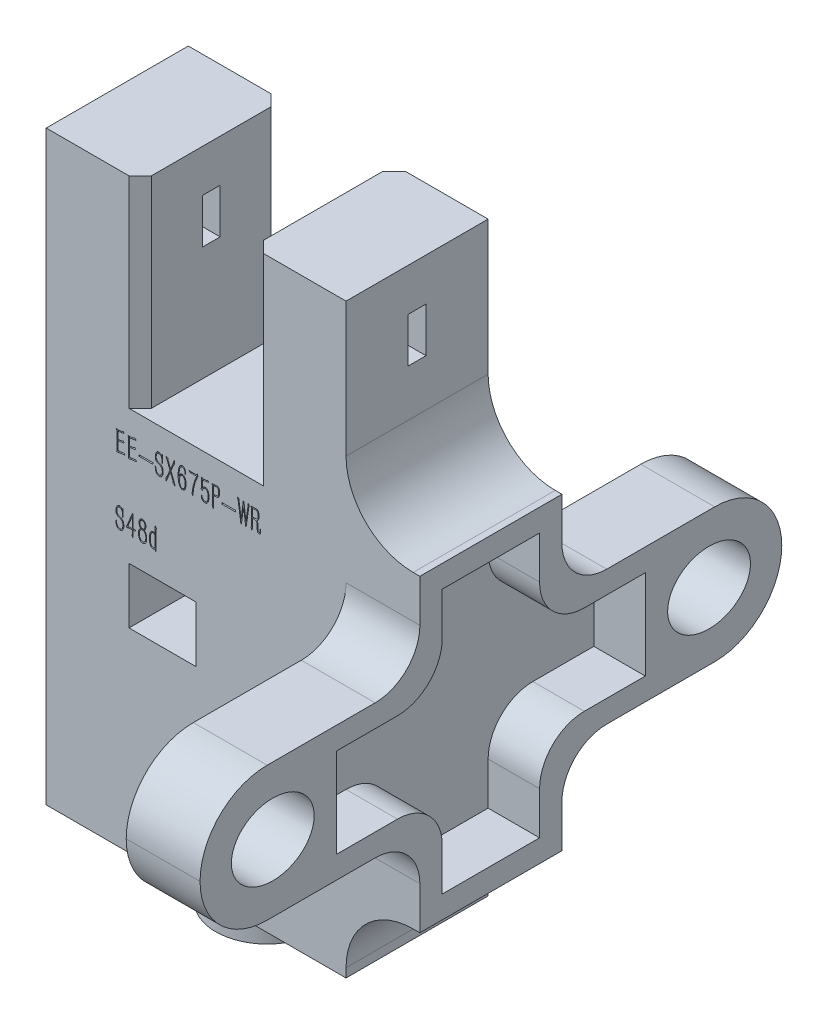
SolidWorks part; units mm, degrees
ref_plane "前视基准面" through (0, 0, 0) normal (0, 0, 1) x (1, 0, 0)
ref_plane "上视基准面" through (0, 0, 0) normal (0, 1, 0) x (1, 0, 0)
ref_plane "右视基准面" through (0, 0, 0) normal (1, 0, 0) x (0, 0, -1)
sketch "草图1" plane through (0, 0, 0) normal (0, 0, 1) x (1, 0, 0)
  line L12 (-6.7, 9) -> (-2.5, 9)
  line L13 (-2.5, 9) -> (-2.5, 0)
  line L14 (-2.5, 0) -> (2.5, 0)
  line L15 (2.5, 0) -> (2.5, 9)
  line L16 (2.5, 9) -> (6.7, 9)
  line L17 (6.7, 9) -> (6.7, 0)
  line L21 (6.7, -12.4475) -> (6.7, -17.2)
  line L22 (6.7, -17.2) -> (-6.7, -17.2)
  line L23 (-6.7, -17.2) -> (-6.7, 9)
  line L24 (0, 0) -> (0, 14.9355) construction
  line L25 (6.7, 0) -> (6.7, -12.4475)
  line L26 (-3, -8.5) -> (0, -8.5)
  line L27 (-3, -8.5) -> (-3, -6)
  line L28 (-3, -6) -> (0, -6)
  line L29 (0, -8.5) -> (0, -6)
  point P10 (0, 0)
  dimension "D1" = 13.4
  dimension "D2" = 5
  dimension "D3" = 9
  dimension "D4" = 8.5
  dimension "D5" = 2.5
  dimension "D6" = 3
  dimension "D7" = 6.7
  dimension "D8" = 13.4
  dimension "D10" = 26.2
extrude "凸台-拉伸1" add sketch "草图1" along normal blind 6.35
sketch "草图2" plane through (6.7, 0, 0) normal (1, 0, 0) x (0, 0, -1)
  line L0 (-16.175, -6.9) -> (11.6328, -6.9) construction
  line L1 (-6.35, -17.2) -> (0, -17.2) construction
  line L2 (-6.35, -3.9) -> (-16.175, -3.9)
  line L3 (-6.35, -17.2) -> (-6.35, 9) construction
  line L4 (-16.175, -3.9) -> (-16.175, -9.9)
  line L5 (-3.175, 9) -> (-3.175, 2.4392) construction
  line L6 (-6.35, 9) -> (0, 9) construction
  line L7 (0, -3.9) -> (9.825, -3.9)
  line L8 (9.825, -3.9) -> (9.825, -9.9)
  line L9 (-6.35, -9.9) -> (-16.175, -9.9)
  line L10 (0, -9.9) -> (9.825, -9.9)
  line L11 (-9.0117, 6.1) -> (2.8445, 6.1) construction
  line L12 (-3.575, 5.1) -> (-3.575, 7.1)
  line L13 (-3.575, 7.1) -> (-2.775, 7.1)
  line L14 (-2.775, 5.1) -> (-2.775, 7.1)
  line L15 (-3.575, 5.1) -> (-2.775, 5.1)
  line L16 (-6.35, -3.9) -> (0, -3.9)
  line L17 (-6.35, -9.9) -> (0, -9.9)
  line L18 (-6.35, -3.9) -> (-6.35, 0)
  line L19 (-6.35, 0) -> (0, 0)
  line L20 (0, 0) -> (0, -3.9)
  line L21 (-6.35, -9.9) -> (-6.35, -13.8)
  line L22 (-6.35, -13.8) -> (0, -13.8)
  line L23 (0, -17.2) -> (0, 9) construction
  line L24 (0, -13.8) -> (0, -9.9)
  line L25 (-5.35, -1) -> (-1, -1)
  line L26 (-1, -1) -> (-1, -4.9)
  line L27 (-1, -4.9) -> (3.725, -4.9)
  line L28 (3.725, -4.9) -> (3.725, -8.9)
  line L29 (3.725, -8.9) -> (-1, -8.9)
  line L30 (-1, -8.9) -> (-1, -12.8)
  line L31 (-1, -12.8) -> (-5.35, -12.8)
  line L32 (-5.35, -12.8) -> (-5.35, -8.9)
  line L33 (-5.35, -8.9) -> (-10.075, -8.9)
  line L34 (-10.075, -8.9) -> (-10.075, -4.9)
  line L35 (-10.075, -4.9) -> (-5.35, -4.9)
  line L36 (-5.35, -4.9) -> (-5.35, -1)
  ellipse E0 centre (-12.925, -6.9) end of major axis (-11.075, -6.9) minor radius 1.6
  ellipse E1 centre (6.575, -6.9) end of major axis (8.425, -6.9) minor radius 1.6
  point P30 (9.825, -6.9)
  point P37 (-3.175, 7.1)
  point P39 (-2.775, 6.1)
  point P40 (-3.575, 6.1)
  point P59 (-6.35, -11.85)
  line M11 (0, -17.2) -> (0, 9)
  line M13 (-6.35, 9) -> (-6.35, -17.2)
  dimension "D4" = 3.7
  dimension "D5" = 3
  dimension "D1" = 10.3
  dimension "D2" = 3.2
  dimension "D3" = 26
  dimension "D6" = 19.5
  dimension "D7" = 13
  dimension "D8" = 0.4
  dimension "D9" = 1
  dimension "D10" = 3.9
  dimension "D11" = 1
  dimension "D12" = 1
  dimension "D13" = 1
  dimension "D14" = 1
  dimension "D15" = 1
  dimension "D16" = 1
  dimension "D17" = 1
  dimension "D18" = 1
  dimension "D19" = 1
  dimension "D20" = 1
  dimension "D21" = 1
  dimension "D22" = 1
extrude "切除-拉伸1" cut sketch "草图2" against normal blind 16.35 contours L12 L15 L14 L13 region at (6.7, 6.1, 3.175)
extrude "凸台-拉伸2" add sketch "草图2<4>" along normal blind 1 contours L9 L2 L4 E0 M13 | L19 L16 M13 M11 | L22 L17 M13 M11 | L10 L8 L7 E1 M11 | L35 L36 L16 M13 | L26 L27 L16 M11 | L29 L30 L17 M11 | L32 L33 L17 M13 | L35 L34 L33 M13 | L36 L35 L33 L32 L17 L30 L29 L27 L26 L16 M13 M11 | L36 L16 L26 L25 | L32 L31 L30 L17 | L29 L28 L27 M11 region at (6.7, -4.4, 6.4651) region at (6.7, -1.95, 6.2755) region at (6.7, -4.4, 5.85) region at (6.7, -2.45, 3.175) region at (6.7, -6.9, 3.175) region at (6.7, -6.9, 8.2125) region at (6.7, -4.4, 0.5) region at (6.7, -9.4, 5.85) region at (6.7, -9.9745, 5.85) region at (6.7, -4.0151, -4.9125) region at (6.7, -11.35, 3.175) region at (6.7, -6.9, -1.8625) region at (6.7, -9.4, 0.5)
sketch "草图2<4>" plane through (6.7, 0, 0) normal (1, 0, 0) x (0, 0, -1) same geometry as "草图2"
sketch "草图3" plane through (0, -17.2, 0) normal (0, -1, 0) x (1, 0, 0)
  line L0 (0, 0) -> (0, 6.35) construction
  line L1 (-6.7, 0) -> (6.7, 0) construction
  line L2 (-6.7, 6.35) -> (6.7, 6.35) construction
  circle A0 centre (0, 3.175) radius 2.3
  dimension "D1" = 4.6
extrude "凸台-拉伸3" add sketch "草图3" along normal blind 2
chamfer "倒角1" distance 0.5 angle 45 4 edges at (2.5, 4.5, 6.35) (2.5, 4.5, 0) (-2.5, 4.5, 0) (-2.5, 4.5, 6.35)
extrude "凸台-拉伸5" add sketch "草图2<8>" along normal blind 3.3 contours L34 L35 L2 L4 L9 L33 E0 M13 | L35 L36 L16 M13 | L16 L36 L25 L26 L19 M11 M13 | L26 L27 L16 M11 | L28 L29 L10 L8 L7 L27 E1 M11 | L31 L32 L17 L22 L30 M13 M11 | L32 L33 L17 M13 | L29 L30 L17 M11 region at (6.7, -4.4, 6.4651) region at (6.7, -1.95, 6.2755) region at (6.7, -4.4, 5.85) region at (6.7, -4.4, 0.5) region at (6.7, -9.4, 5.85) region at (6.7, -9.9745, 5.85) region at (6.7, -4.0151, -4.9125) region at (6.7, -9.4, 0.5)
sketch "草图2<8>" plane through (6.7, 0, 0) normal (1, 0, 0) x (0, 0, -1) same geometry as "草图2"
fillet "圆角3" radius 3 4 edges at (8.35, -9.9, -9.825) (8.35, -3.9, -9.825) (8.35, -9.9, 16.175) (8.35, -3.9, 16.175)
fillet "圆角4" radius 2 8 edges at (8.85, -8.9, 1) (8.85, -8.9, 5.35) (8.85, -4.9, 1) (8.85, -4.9, 5.35) (8.35, -9.9, 0) (8.35, -9.9, 6.35) (8.35, -3.9, 0) (8.35, -3.9, 6.35)
fillet "圆角5" radius 3 2 edges at (6.7, -13.8, 3.175) (6.7, 0, 3.175)
sketch "草图4" plane through (0, 0, 6.35) normal (0, 0, 1) x (1, 0, 0)
  text T0 "EE-SX675P-WR\r\nS48d" font "汉仪长仿宋体" height 1
extrude "切除-拉伸2" cut sketch "草图4" against normal blind 1
